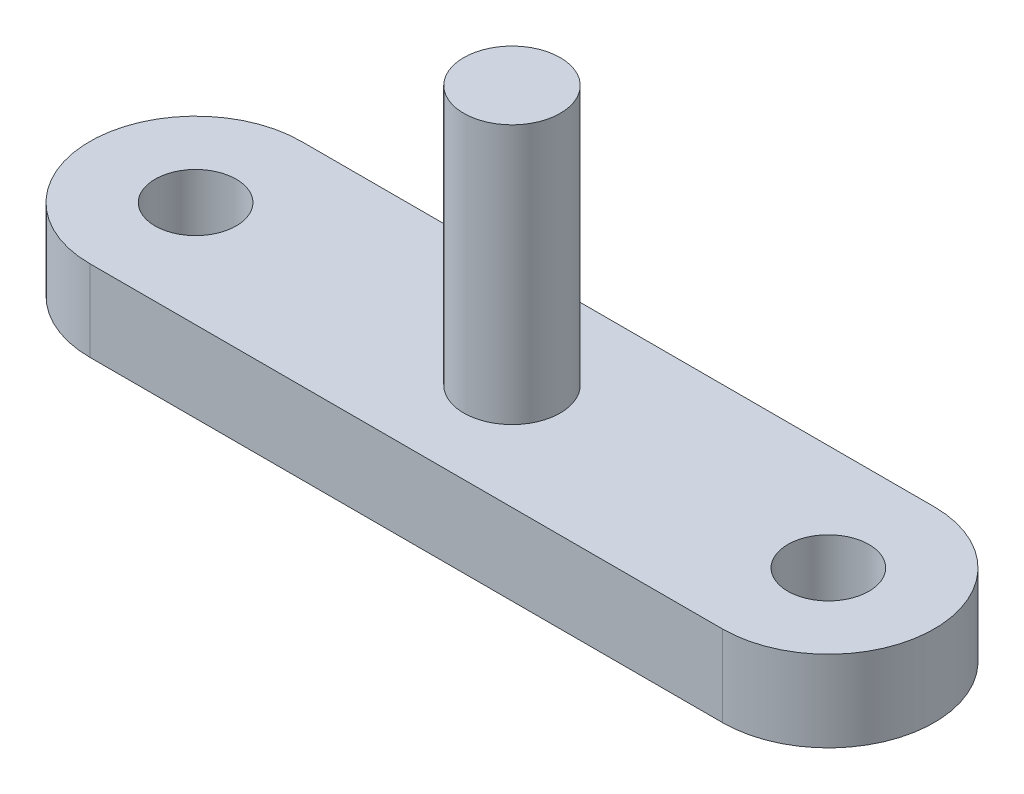
SolidWorks part; units mm, degrees
material "Acero aleado"
ref_plane "Alzado" through (0, 0, 0) normal (0, 0, 1) x (1, 0, 0)
ref_plane "Planta" through (0, 0, 0) normal (0, 1, 0) x (1, 0, 0)
ref_plane "Vista lateral" through (0, 0, 0) normal (1, 0, 0) x (0, 0, -1)
sketch "Croquis2" plane through (0, 0, 0) normal (0, 1, 0) x (1, 0, 0)
  line L0 (-19.5, 0) -> (19.5, 0)
  line L1 (-19.5, 0) -> (19.5, 0) construction
  line L2 (-19.5, 6.5237) -> (19.5, 6.5237)
  line L3 (-19.5, -6.5237) -> (19.5, -6.5237)
  arc A0 (-19.5, 6.5237) -> (-19.5, -6.5237) centre (-19.5, 0) ccw
  arc A1 (19.5, -6.5237) -> (19.5, 6.5237) centre (19.5, 0) ccw
  circle A2 centre (0, 0) radius 2.975
  circle A3 centre (19.5, 0) radius 2.5
  circle A4 centre (-19.5, 0) radius 2.5
  point P4 (0, 0)
  point P6 (0, 0)
  dimension "D2" = 5.95
  dimension "D3" = 5
  dimension "D4" = 5
  dimension "D1" = 39
extrude "Saliente-Extruir1" add sketch "Croquis2" along normal blind 5 contours L3 A1 L2 A0 A4 A2 A3 region at (0, 0, -5.9872)
extrude "Saliente-Extruir2" add sketch "Croquis2<4>" along normal blind 21 contours L0 A2 | L0 A2 region at (0, 0, -1.2626) region at (0, 0, 1.2626)
sketch "Croquis2<4>" plane through (0, 0, 0) normal (0, 1, 0) x (1, 0, 0) same geometry as "Croquis2"
